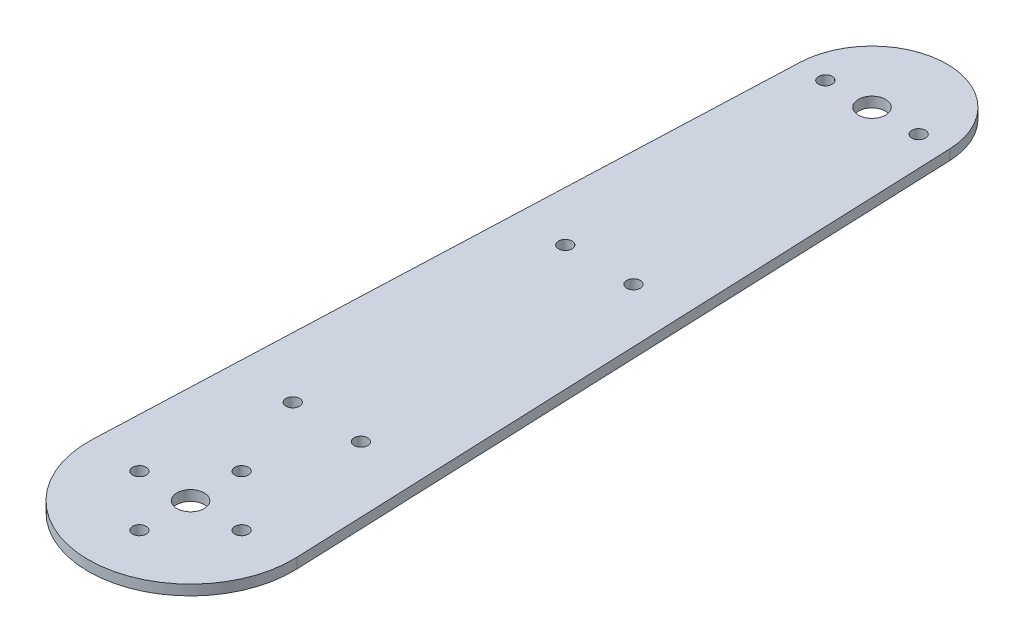
SolidWorks part; units mm, degrees
note: The reader was unsure of these and kept them because the rebuilt part matched: thickness of "基体-法兰1", "钣金6".
material "7075-T6，板材(SS)"
ref_plane "前视基准面" through (0, 0, 0) normal (0, 0, 1) x (1, 0, 0)
ref_plane "上视基准面" through (0, 0, 0) normal (0, 1, 0) x (1, 0, 0)
ref_plane "右视基准面" through (0, 0, 0) normal (1, 0, 0) x (0, 0, -1)
sketch "草图1" plane through (0, 0, 0) normal (0, 1, 0) x (1, 0, 0)
  line L0 (0, 0) -> (0, 181.2198) construction
  line L1 (21.9824, 200.88) -> (29.976, 1.2)
  line L2 (-21.9824, 200.88) -> (-29.976, 1.2)
  line L4 (-1000, 200) -> (49000, 200) construction
  line L5 (0, -800) -> (0, 49200) construction
  arc A0 (-29.976, 1.2) -> (29.976, 1.2) centre (0, 0) ccw
  arc A1 (21.9824, 200.88) -> (-21.9824, 200.88) centre (0, 200) ccw
  circle A2 centre (0, 0) radius 4
  circle A3 centre (0, 200) radius 4
  circle A4 centre (10, 120) radius 2
  circle A5 centre (-10, 120) radius 2
  circle A6 centre (10, 40) radius 2
  circle A7 centre (-10, 40) radius 2
  circle A12 centre (0, 15) radius 2
  circle A13 centre (15, 0) radius 2
  circle A14 centre (0, -15) radius 2
  circle A15 centre (-15, 0) radius 2
  circle A18 centre (-13.693, 200) radius 2
  circle A19 centre (13.693, 200) radius 2
  point P28 (0, 0)
  point P30 (0, 0)
  dimension "D1" = 60
  dimension "D2" = 44
  dimension "D4" = 8
  dimension "D5" = 8
  dimension "D6" = 4
  dimension "D7" = 4
  dimension "D8" = 4
  dimension "D9" = 4
  dimension "D18" = 4
  dimension "D19" = 4
  dimension "D3" = 200
  dimension "D10" = 10
  dimension "D11" = 10
  dimension "D12" = 10
  dimension "D13" = 10
  dimension "D14" = 40
  dimension "D15" = 40
  dimension "D16" = 80
  dimension "D17" = 80
base flange "基体-法兰1" sketch "草图1" thickness 3 reverse thickness direction no parameters "D1"=0.7366
sketch "折弯-线1" [suppressed] plane through (0, 0, 0) normal (0, 1, 0) x (1, 0, 0)
sketch "边界框1" [suppressed] plane through (0, 0, 0) normal (0, 1, 0) x (1, 0, 0)
sheet metal parameters "钣金6" thickness 3 parameters "D1"=0.7366
flat pattern "平板型式6" [suppressed]
sketch "折弯-线2" plane through (0, 0, 0) normal (0, 1, 0) x (1, 0, 0)
sketch3d "边界框2" [suppressed]
  line L0 (38.8496, 20.4624, 0) -> (28.776, -231.176, 0) construction
  line L1 (-21.1024, 22.8624, 0) -> (-31.176, -228.776, 0) construction
  line L2 (38.8496, 20.4624, 0) -> (-21.1024, 22.8624, 0) construction
  line L3 (28.776, -231.176, 0) -> (-31.176, -228.776, 0) construction
